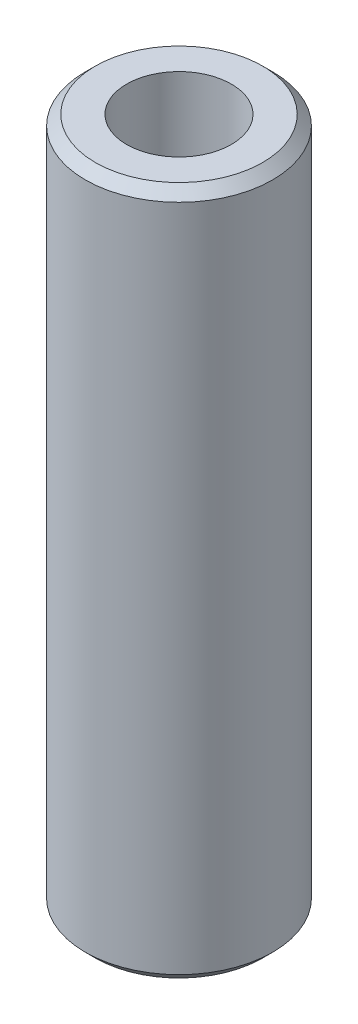
SolidWorks part; units mm, degrees
ref_plane "Front Plane" through (0, 0, 0) normal (0, 0, 1) x (1, 0, 0)
ref_plane "Top Plane" through (0, 0, 0) normal (0, 1, 0) x (1, 0, 0)
ref_plane "Right Plane" through (0, 0, 0) normal (1, 0, 0) x (0, 0, -1)
sketch "Sketch1" plane through (0, 0, 0) normal (0, 1, 0) x (1, 0, 0)
  circle A0 centre (0, 0) radius 45
  dimension "SHAFT_OD" = 90
extrude "Boss-Extrude1" add sketch "Sketch1" along normal blind 331.0122
sketch "Sketch2" plane through (0, 0, 0) normal (0, 1, 0) x (1, 0, 0)
  circle A0 centre (0, 0) radius 25.1619
  dimension "BORE_D" = 50.3238
extrude "Cut-Extrude1" cut sketch "Sketch2" along normal through all
chamfer "Chamfer1" distance 4.8148 angle 45 2 edges at (0, 331.0122, 45) (0, 0, 45)
